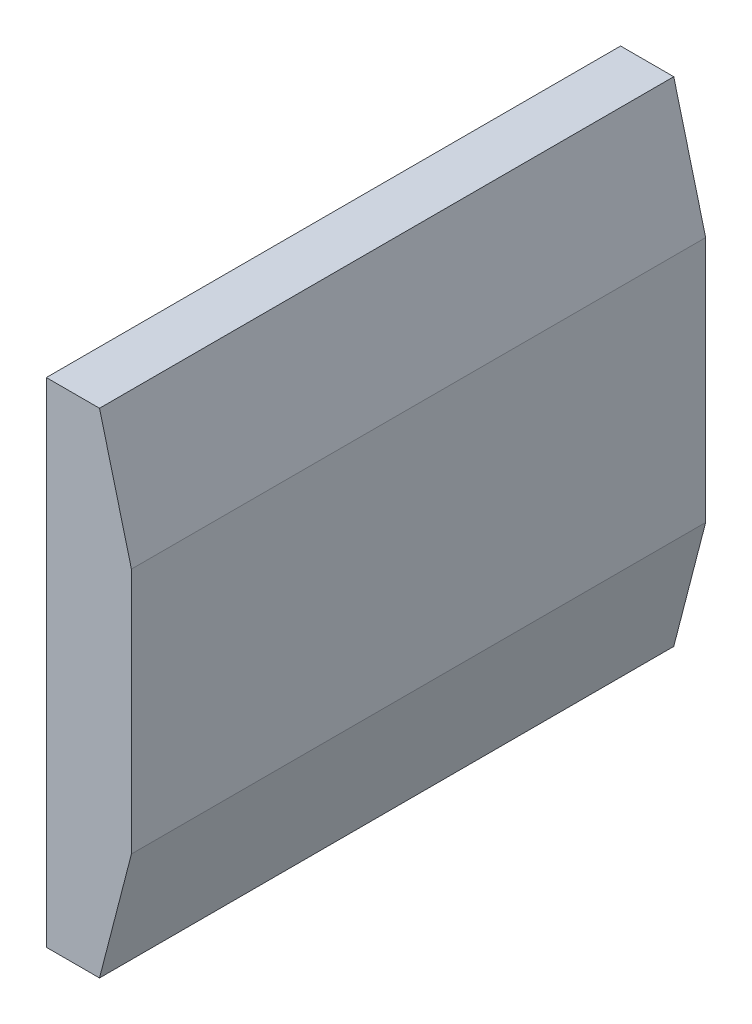
SolidWorks part; units mm, degrees
ref_plane "Front Plane" through (0, 0, 0) normal (0, 0, 1) x (1, 0, 0)
ref_plane "Top Plane" through (0, 0, 0) normal (0, 1, 0) x (1, 0, 0)
ref_plane "Right Plane" through (0, 0, 0) normal (1, 0, 0) x (0, 0, -1)
sketch "Sketch1" plane through (0, 0, 0) normal (0, 0, 1) x (1, 0, 0)
  line L1 (0, 0) -> (5, 0)
  line L2 (0, 0) -> (0, -116)
  line L3 (0, -116) -> (5, -116)
  line L4 (5, 0) -> (5, -116)
  line L5 (5, 0) -> (20, 0)
  line L6 (5, 0) -> (5, -116)
  line L7 (5, -116) -> (20, -116)
  line L8 (20, 0) -> (20, -116)
  line L9 (20, -58) -> (20, 0)
  line L10 (12.5, 0) -> (20, -29)
  line L11 (20, -29) -> (20, -58)
  line L13 (20, -58) -> (20, -116)
  line L14 (20, -87) -> (12.5, -116)
  dimension "D1" = 5
  dimension "D2" = 116
  dimension "D3" = 15
extrude "Boss-Extrude1" add sketch "Sketch1" along normal blind 67.5 and the other way blind 67.5 contours L14 L8 L9 L10 L5 L4 L7 | L4 L1 L2 L3 region at (2.5, -58, 0) region at (11.7857, -58, 0)
